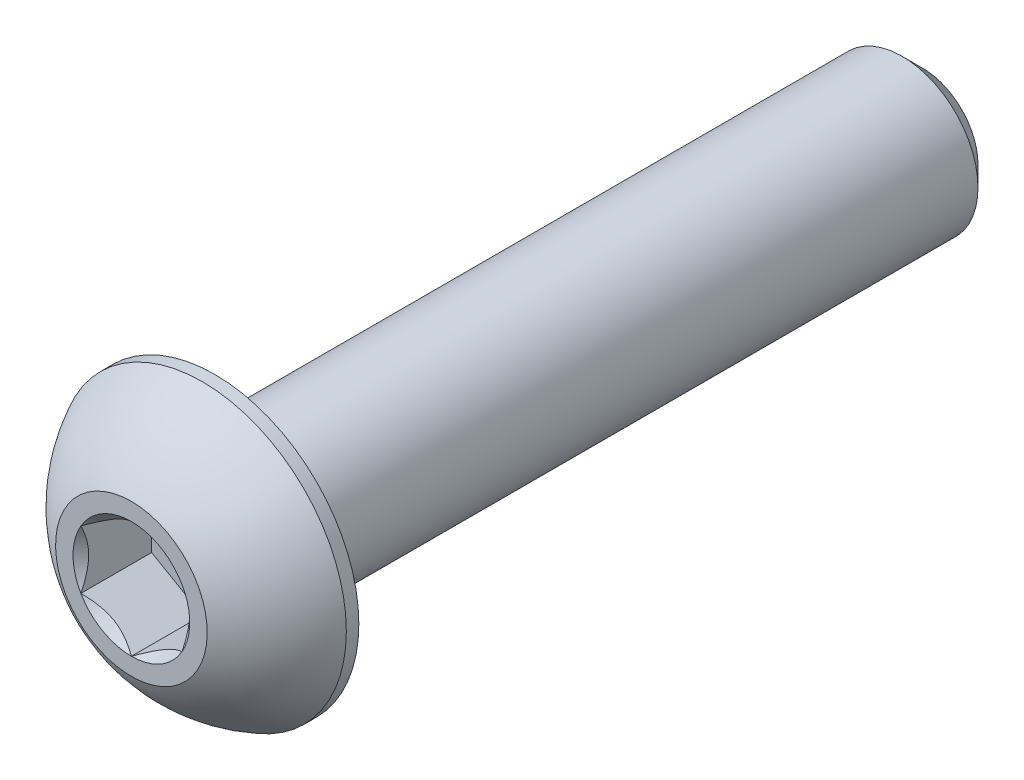
SolidWorks part; units mm, degrees
material "Alloy Steel"
ref_plane "Front Plane" through (0, 0, 0) normal (0, 0, 1) x (1, 0, 0)
ref_plane "Top Plane" through (0, 0, 0) normal (0, 1, 0) x (1, 0, 0)
ref_plane "Right Plane" through (0, 0, 0) normal (1, 0, 0) x (0, 0, -1)
sketch "Sketch1" plane through (0, 0, 0) normal (1, 0, 0) x (0, 0, -1)
  line L0 (-7.825, 0) -> (7.825, 0) construction
  line L1 (-6.175, 2.85) -> (-6.175, -2.85) construction
  line L2 (7.825, 1.5) -> (7.825, -1.5) construction
  line L3 (7.7937, 1.5541) -> (8.0437, 1.1211) construction
  line L4 (8.0437, 1.1211) -> (8.2937, 1.5541) construction
  line L5 (8.2937, 1.5541) -> (7.7937, 1.5541) construction
  line L6 (7.825, 1.5) -> (8.2625, 1.5) construction
  line L7 (8.0437, 1.5541) -> (8.0437, 1.5) construction
  line L8 (8.0437, 1.5) -> (8.0437, 1.1752) construction
  line L9 (8.0437, 1.1752) -> (8.0437, 1.1211) construction
  line L10 (8.0125, 1.1752) -> (8.075, 1.1752)
  line L11 (7.8094, 1.5271) -> (8.2781, 1.5271)
  line L12 (8.075, 1.1752) -> (8.2781, 1.5271)
  line L13 (8.0125, 1.1752) -> (7.8094, 1.5271)
  line L14 (-7.825, 1) -> (-7.825, -1) construction
  line L15 (7.825, 1.5) -> (-6.175, 1.5) construction
  point P3 (-6.175, 0)
  point P6 (-6.425, 0)
  point P21 (8.0437, 1.5271)
  point P24 (-6.4225, 2.85)
  point P25 (6.575, -1.5)
  point P26 (-7.825, 1.5)
  dimension "Head Height" = 1.65
  dimension "Length" = 14
  dimension "Head Dia" = 5.7
  dimension "Thread Dia" = 3
  dimension "Pitch" = 0.5
  dimension "D2" = 0.0625
  dimension "Drive Size" = 2
  dimension "D1" = 1.4
  dimension "D3" = 0.2475
  dimension "D4" = 1.25
sketch "Sketch2" plane through (0, 0, 0) normal (1, 0, 0) x (0, 0, -1)
  line L0 (-7.825, 0) -> (7.825, 0)
  line L1 (7.825, 0) -> (7.825, 1.1)
  line L2 (7.825, 1.5) -> (7.825, -1.5) construction
  line L3 (7.825, 1.1) -> (7.425, 1.5)
  line L4 (7.425, 1.5) -> (-6.175, 1.5)
  line L5 (-6.175, 2.85) -> (-6.175, -2.85) construction
  line L6 (-6.175, 1.5) -> (-6.175, 2.85)
  line L7 (-6.175, 2.85) -> (-6.4225, 2.85)
  line L8 (7.825, 1.5) -> (8.2625, 1.5) construction
  line L9 (-7.825, 0) -> (-7.825, 1.5)
  arc A0 (-7.825, 1.5) -> (-6.4225, 2.85) centre (-5.0302, 0) cw
  dimension "D1" = 0.4
  dimension "D2" = 45
revolve "Revolve1" add sketch "Sketch2" angle 360 about L0
sketch "Sketch3" plane through (0, 0, 7.825) normal (0, 0, 1) x (1, 0, 0)
  line L1 (0, 1.1547) -> (-1, 0.5774)
  line L2 (-1, 0.5774) -> (-1, -0.5774)
  line L3 (-1, -0.5774) -> (0, -1.1547)
  line L4 (0, -1.1547) -> (1, -0.5774)
  line L5 (1, -0.5774) -> (1, 0.5774)
  line L6 (1, 0.5774) -> (0, 1.1547)
  circle A0 centre (0, 0) radius 1 construction
  dimension "D1" = 2
extrude "Cut-Extrude1" cut sketch "Sketch3" against normal up to vertex (1.4 mm away) up to point (0, 0, 6.425)
sketch "Sketch4" plane through (0, 0, 7.825) normal (0, 0, 1) x (1, 0, 0)
  circle A0 centre (0, 0) radius 1.1547
extrude "Cut-Extrude2" cut sketch "Sketch4" against normal blind 10 draft 45
split "Split1" [suppressed] bodies to split 106
sketch "Sketch5" [suppressed] plane through (0, 0, -7.825) normal (0, 0, -1) x (-1, 0, 0)
  circle A0 centre (0, 0) radius 1.5 construction
  circle A1 centre (0, 0) radius 1.5
curve "Helix/Spiral1" [suppressed] pitch 0.5 height 14.5 turns 29
sketch "Sketch6" [suppressed] plane through (0, 0, 0) normal (1, 0, 0) x (0, 0, -1)
  line L0 (8.0125, 1.1752) -> (8.075, 1.1752) construction
  line L1 (8.0125, 1.1752) -> (7.8094, 1.5271) construction
  line L2 (7.8094, 1.5271) -> (8.2781, 1.5271) construction
  line L3 (8.075, 1.1752) -> (8.2781, 1.5271) construction
  line L4 (8.0125, 1.1752) -> (8.075, 1.1752)
  line L5 (8.0125, 1.1752) -> (7.8094, 1.5271)
  line L6 (7.8094, 1.5271) -> (8.2781, 1.5271)
  line L7 (8.075, 1.1752) -> (8.2781, 1.5271)
sweep "Cut-Sweep1" [suppressed] cut profiles "Sketch6" path "Helix/Spiral1"
sketch "Sketch7" [suppressed] plane through (0, 0, 6.175) normal (0, 0, -1) x (-1, 0, 0)
  circle A1 centre (0, 0) radius 1.5
  circle A2 centre (0, 0) radius 1.5
  dimension "D1" = 0
extrude "Boss-Extrude1" [suppressed] add sketch "Sketch7" along normal blind 10 draft 30
equation "\"D2@Sketch1\" = \"Pitch@Sketch1\" / 8"
equation "\"D1@Sketch1\"=\"Drive Size@Sketch1\"*.7"
equation "\"D3@Sketch1\"=\"Head Height@Sketch1\"*.15"
equation "\"D1@Sketch2\"=\"Pitch@Sketch1\"*.8"
equation "\"D1@Sketch3\"=\"Drive Size@Sketch1\""
equation "\"D4@Helix/Spiral1\"=\"Pitch@Sketch1\""
equation "\"D3@Helix/Spiral1\"=\"Length@Sketch1\"+\"Pitch@Sketch1\""
equation "\"D4@Sketch1\"=\"Pitch@Sketch1\"*2.5"
